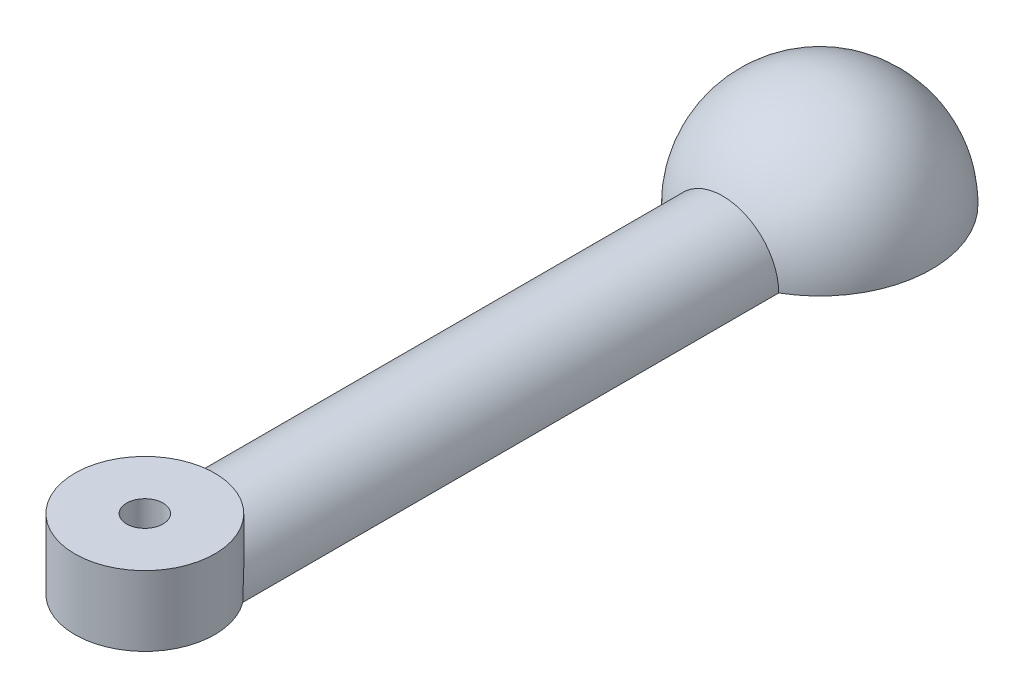
SolidWorks part; units mm, degrees
ref_plane "Front Plane" through (0, 0, 0) normal (0, 0, 1) x (1, 0, 0)
ref_plane "Top Plane" through (0, 0, 0) normal (0, 1, 0) x (1, 0, 0)
ref_plane "Right Plane" through (0, 0, 0) normal (1, 0, 0) x (0, 0, -1)
sketch "Sketch1" plane through (0, 0, 0) normal (0, 0, 1) x (1, 0, 0)
  circle A0 centre (0, 0) radius 10.16
  dimension "D1" = 20.32
extrude "Boss-Extrude1" add sketch "Sketch1" along normal blind 101.6
sketch "Sketch2" plane through (0, 0, 0) normal (1, 0, 0) x (0, 0, -1)
  line L0 (55, 0) -> (-55, 0) construction
  line L1 (-2.7224, 0) -> (37.9176, 0)
  circle A0 centre (17.5976, 0) radius 20.32
  dimension "D1" = 40.64
revolve "Revolve1" add sketch "Sketch2" angle 360 about L1 region at (0, 8.6241, -17.5976)
sketch "Sketch3" plane through (0, 0, 0) normal (0, 1, 0) x (1, 0, 0)
  line L0 (0, -22.352) -> (0, 22.352) construction
  line L1 (-10.16, -101.6) -> (10.16, -101.6) construction
  circle A0 centre (0, -104.902) radius 12.7
  circle A1 centre (0, -104.902) radius 3.302
  point P5 (0, -105.2821)
  dimension "D1" = 6.604
  dimension "D2" = 25.4
extrude "Boss-Extrude2" add sketch "Sketch3" along normal mid plane 25.4
sketch "Sketch5" plane through (0, 0, 0) normal (0, 1, 0) x (1, 0, 0)
  line L1 (-24.3212, 47.5698) -> (26.0069, 47.5698)
  line L2 (-24.3212, 47.5698) -> (-24.3212, -130.1438)
  line L3 (-24.3212, -130.1438) -> (26.0069, -130.1438)
  line L4 (26.0069, 47.5698) -> (26.0069, -130.1438)
  line L5 (-24.3212, 47.5698) -> (26.0069, -130.1438) construction
  line L6 (-24.3212, -130.1438) -> (26.0069, 47.5698) construction
  point P4 (0.8428, -41.287)
extrude "Cut-Extrude2" cut sketch "Sketch5" against normal through all
sketch "Sketch4" plane through (0, 0, 0) normal (0, 1, 0) x (1, 0, 0)
  line L0 (-10.16, -87.162) -> (-10.16, -92.162)
  line L1 (-1.524, 29.1546) -> (1.524, 29.1546)
  line L2 (-1.524, 29.1546) -> (-1.524, 6.0406)
  line L4 (1.524, 29.1546) -> (1.524, 6.0406)
  line L5 (-1.524, 29.1546) -> (1.524, 6.0406) construction
  line L6 (-1.524, 6.0406) -> (1.524, 29.1546) construction
  line L7 (2.5, 6.0406) -> (-2.5, 6.0406)
  line L8 (2.5, 6.0406) -> (2.5, -79.502)
  line L9 (2.5, -79.502) -> (-2.5, -79.502)
  line L10 (-2.5, 6.0406) -> (-2.5, -79.502)
  line L12 (-15.16, -92.162) -> (-10.16, -92.162) construction
  line L13 (-10.16, 0) -> (-10.16, -97.282) construction
  line L14 (0, -11.6449) -> (0, 11.6449) construction
  line L15 (0, -79.502) -> (0, -104.902) construction
  line L19 (-2.5, 6.0406) -> (-2.5, 11.0406)
  line L20 (-2.5, 11.0406) -> (-1.524, 11.0406)
  line L22 (-2.5, 6.0406) -> (-1.524, 11.0406) construction
  line L23 (-2.5, 11.0406) -> (-1.524, 6.0406) construction
  line L24 (-1.524, 29.1546) -> (-2.5, 29.1546)
  line L26 (-1.524, 24.1546) -> (-2.5, 24.1546)
  line L27 (-2.5, 29.1546) -> (-2.5, 24.1546)
  line L28 (-1.524, 29.1546) -> (-2.5, 24.1546) construction
  line L29 (-1.524, 24.1546) -> (-2.5, 29.1546) construction
  arc A0 (2.5, -79.502) -> (-10.16, -92.162) centre (-10.16, -79.502) cw
  arc A1 (-10.16, -87.162) -> (-2.5, -79.502) centre (-10.16, -79.502) ccw
  circle A2 centre (-11.43, 17.5976) radius 3.175
  circle A3 centre (11.43, 17.5976) radius 3.175
  circle A4 centre (0, -92.202) radius 3.175
  circle A5 centre (0, 17.5976) radius 20.32 construction
  arc A6 (10.16, 0) -> (-10.16, 0) centre (0, 17.5976) ccw construction
  arc A7 (-10.16, -97.282) -> (10.16, -97.282) centre (0, -104.902) ccw construction
  circle A8 centre (0, -104.902) radius 3.302 construction
  point P4 (0, 17.5976)
  point P9 (0, -37.3022)
  point P14 (0, 0)
  point P15 (-10.9189, -92.9209)
  point P20 (0, -79.502)
  point P34 (0, -104.902)
  point P39 (0, -104.902)
  point P40 (-2.012, 26.6546)
  point P41 (0, 0)
  point P45 (0, -92.202)
  point P46 (0, -92.202)
  point P49 (0, 0)
  point P52 (-2.012, 8.5406)
  dimension "D3" = 6.35
  dimension "D1" = 3.048
  dimension "D2" = 23.114
  dimension "D4" = 11.43
  dimension "D5" = 11.43
  dimension "D6" = 5
extrude "Cut-Extrude3" cut sketch "Sketch4" along normal blind 11.684
extrude "Cut-Extrude4" cut sketch "Sketch4<3>" along normal blind 6.35 draft 5 contours L7 L10 L9 L8 | A1 L0 A0 L9 region at (-3.5614, 0, 86.1006) region at (0, 0, 36.7307)
sketch "Sketch4<3>" plane through (0, 0, 0) normal (0, 1, 0) x (1, 0, 0) same geometry as "Sketch4"
sketch "Sketch7" plane through (-10.0828, 0.8821, 0) normal (0.9962, -0.0872, 0) x (0, 0, -1)
  line L0 (-92.162, -0.8855) -> (-92.0067, 0.8855)
  line L1 (0, 0.8855) -> (-97.282, 0.8855) construction
  line L2 (-92.0067, 0.8855) -> (-87.3148, 0.8855)
  line L3 (-87.3148, 0.8855) -> (-87.162, -0.8855)
  line L4 (-87.162, -0.8855) -> (-92.162, -0.8855)
  point P9 (-92.2707, 0.8855)
  point P10 (-92.162, -0.8855)
  point P13 (-87.162, -0.8855)
  point P15 (-92.0067, 0.8855)
  point P17 (-87.3148, 0.8855)
extrude "Cut-Extrude5" cut sketch "Sketch7" against normal through all
extrude "Boss-Extrude3" add sketch "Sketch4<5>" along normal mid plane 6.35 draft 2 contours A2 | A3 | A4 region at (-11.43, 0, -17.5976) region at (11.43, 0, -17.5976)
sketch "Sketch4<5>" plane through (0, 0, 0) normal (0, 1, 0) x (1, 0, 0) same geometry as "Sketch4"
